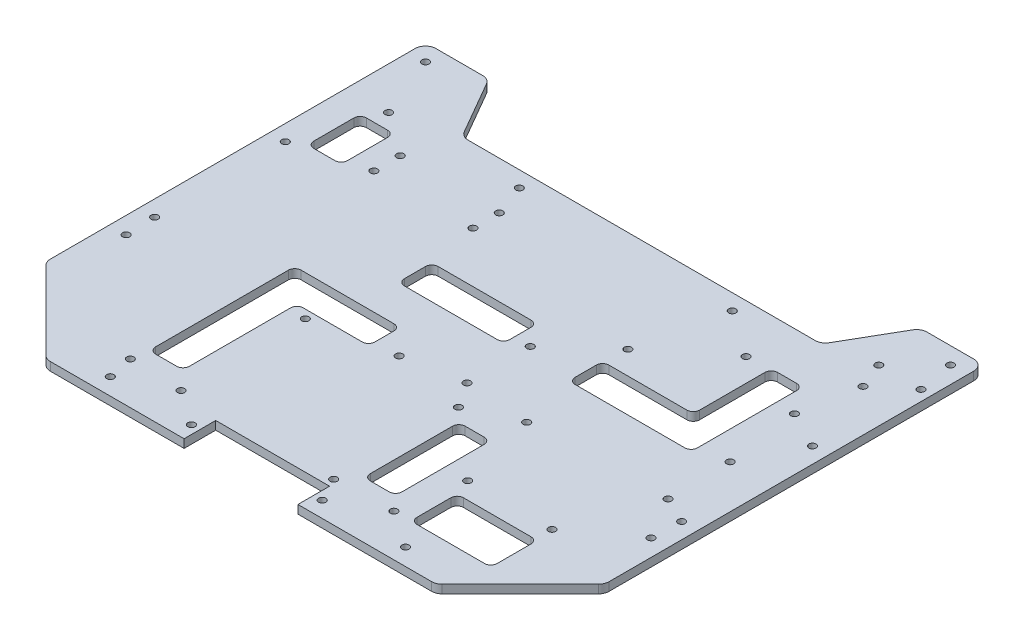
SolidWorks part; units mm, degrees
material "Acier non allié"
ref_plane "Front" through (0, 0, 0) normal (0, 0, 1) x (1, 0, 0)
ref_plane "Top" through (0, 0, 0) normal (0, 1, 0) x (1, 0, 0)
ref_plane "Right" through (0, 0, 0) normal (1, 0, 0) x (0, 0, -1)
sketch "Main scetch" plane through (0, 0, 0) normal (0, 1, 0) x (1, 0, 0)
  line L1 (0, 0) -> (132.5, 0) construction
  line L2 (0, 0) -> (0, 220) construction
  line L3 (0, 220) -> (132.5, 220) construction
  line L4 (132.5, 0) -> (132.5, 220) construction
  line L13 (-92.5, 0) -> (92.5, 0)
  line L14 (92.5, 0) -> (132.5, 40)
  line L15 (132.5, 40) -> (132.5, 220)
  line L16 (132.5, 220) -> (102.5, 220)
  line L17 (102.5, 220) -> (85.1795, 190)
  line L18 (85.1795, 190) -> (-85.1795, 190)
  line L19 (-102.5, 220) -> (-85.1795, 190)
  line L20 (-132.5, 220) -> (-102.5, 220)
  line L21 (-132.5, 40) -> (-132.5, 220)
  line L22 (-92.5, 0) -> (-132.5, 40)
  point P11 (0, 190)
  dimension "132.5" = 132.5
  dimension "D2" = 220
  dimension "D1" = 40
  dimension "D3" = 40
  dimension "D4" = 30
  dimension "D5" = 60
  dimension "D6" = 30
extrude "Main extrusion" add sketch "Main scetch" along normal blind 4
fillet "Congé1" radius 5 10 edges at (-132.5, 2, -40) (-92.5, 2, 0) (92.5, 2, 0) (132.5, 2, -40) (132.5, 2, -220) (102.5, 2, -220) (85.1795, 2, -190) (-85.1795, 2, -190) (-102.5, 2, -220) (-132.5, 2, -220)
sketch "Esquisse1" plane through (0, 4, 0) normal (0, 1, 0) x (1, 0, 0)
  line L0 (0, 0) -> (0, 218.5516) construction
  line L1 (132.5, 42.0711) -> (132.5, 215) construction
  line L2 (127.5, 220) -> (105.3868, 220) construction
  line L3 (-90.4289, 0) -> (90.4289, 0) construction
  circle A0 centre (70, 8) radius 1
  circle A1 centre (124.5, 70) radius 1
  circle A2 centre (124.5, 212) radius 1
  circle A3 centre (-124.5, 212) radius 1
  circle A4 centre (-124.5, 70) radius 1
  circle A5 centre (-70, 8) radius 1
  dimension "D1" = 2
  dimension "D2" = 2
  dimension "D3" = 2
  dimension "D4" = 8
  dimension "D5" = 8
  dimension "D6" = 8
  dimension "D7" = 8
  dimension "D8" = 70
  dimension "D9" = 70
extrude "Enlèv. mat.-Extru.1" cut sketch "Esquisse1" against normal through all
hole_wizard "Dégagement M31" positions "Esquisse2" profile "Esquisse3" hole size "M3" standard "ISO" end condition through all
sketch "Esquisse2" plane through (0, 4, 0) normal (0, 1, 0) x (1, 0, 0)
  point P0 (-124.5, 212)
  point P3 (-124.5, 70)
  point P6 (-70, 8)
  point P9 (70, 8)
  point P12 (124.5, 70)
  point P15 (124.5, 212)
sketch "Esquisse3" plane through (-124.5, 4, -212) normal (1, 0, 0) x (0, 0, 1)
  line L0 (0, 0) -> (0, 4)
  line L1 (0, 4) -> (1.7, 4)
  line L2 (1.7, 4) -> (1.7, 0)
  line L5 (1.7, 0) -> (0, 0)
  line L11 (0, -6.35) -> (0, 107.95) construction
  dimension "Diamètre du perçage jusqu'au prochain" = 3.4
  dimension "Profondeur du perçage jusqu'au prochain" = 4
sketch "Esquisse4" plane through (0, 4, 0) normal (0, 1, 0) x (1, 0, 0)
  line L0 (-132.5, 215) -> (-132.5, 42.0711) construction
  line L1 (-125, 146) -> (-125, 84) construction
  line L2 (82.2927, 190) -> (-82.2927, 190) construction
  line L3 (132.5, 42.0711) -> (132.5, 215) construction
  line L4 (-90.4289, 0) -> (90.4289, 0) construction
  line L5 (127.5, 220) -> (105.3868, 220) construction
  line L8 (-105.3868, 220) -> (-127.5, 220) construction
  line L9 (-31, 7.5) -> (31, 7.5) construction
  line L10 (125, 146) -> (125, 84) construction
  line L11 (-27, 0) -> (27, 0)
  line L12 (-27, 0) -> (-27, 15)
  line L13 (-27, 15) -> (27, 15)
  line L14 (27, 0) -> (27, 15)
  line L15 (50.5, 182.5) -> (112.5, 182.5) construction
  line L16 (-112.5, 182.5) -> (-50.5, 182.5) construction
  circle A1 centre (-68.5, 185) radius 1 construction
  circle A5 centre (72.5, 167) radius 1
  circle A6 centre (41.5, 142) radius 1
  circle A7 centre (107.5, 155) radius 1
  circle A8 centre (127.5, 195) radius 1
  circle A9 centre (112, 120) radius 1
  circle A10 centre (112.5, 90) radius 1
  circle A11 centre (17.2, 120) radius 1
  circle A12 centre (17.2, 90) radius 1
  circle A13 centre (47.5, 88) radius 1
  circle A14 centre (57.5, 50) radius 1
  circle A15 centre (97.5, 50) radius 1
  circle A16 centre (52.5, 20) radius 1
  circle A17 centre (-10, 85) radius 1
  circle A18 centre (-72.5, 20) radius 1
  circle A19 centre (107.5, 195) radius 1
  circle A23 centre (-47.5, 78) radius 1
  circle A24 centre (25.14, 78) radius 1
  circle A25 centre (-47.5, 19.07) radius 1
  circle A26 centre (25.1096, 18.82) radius 1
  circle A27 centre (-92, 167.5) radius 1
  circle A28 centre (-45, 167.5) radius 1
  circle A29 centre (-92, 155) radius 1
  circle A30 centre (-45, 155) radius 1
  circle A31 centre (-125, 146) radius 1
  circle A32 centre (-125, 84) radius 1
  circle A33 centre (-31, 7.5) radius 1
  circle A34 centre (31, 7.5) radius 1
  circle A35 centre (125, 146) radius 1
  circle A36 centre (125, 84) radius 1
  circle A37 centre (50.5, 182.5) radius 1
  circle A38 centre (112.5, 182.5) radius 1
  circle A39 centre (-112.5, 182.5) radius 1
  circle A40 centre (-50.5, 182.5) radius 1
  point P63 (-125, 115)
  point P69 (0, 7.5)
  point P74 (0, 15)
  point P79 (125, 115)
  dimension "D4" = 2
  dimension "D13" = 2
  dimension "D16" = 2
  dimension "D19" = 2
  dimension "D24" = 2
  dimension "D25" = 2
  dimension "D28" = 2
  dimension "D30" = 2
  dimension "D32" = 2
  dimension "D36" = 2
  dimension "D37" = 2
  dimension "D40" = 2
  dimension "D48" = 2
  dimension "D49" = 2
  dimension "D50" = 2
  dimension "D52" = 2
  dimension "D11" = 2
  dimension "D12" = 2
  dimension "D65" = 2
  dimension "D66" = 2
  dimension "D58" = 2
  dimension "D61" = 2
  dimension "D70" = 2
  dimension "D71" = 2
  dimension "D72" = 2
  dimension "D73" = 2
  dimension "D77" = 2
  dimension "D78" = 2
  dimension "D85" = 2
  dimension "D86" = 2
  dimension "D89" = 2
  dimension "D90" = 2
  dimension "D94" = 2
  dimension "D95" = 2
  dimension "D14" = 205
  dimension "D15" = 23
  dimension "D20" = 25
  dimension "D21" = 65
  dimension "D22" = 5
  dimension "D23" = 25
  dimension "D26" = 20.5
  dimension "D27" = 100
  dimension "D29" = 30
  dimension "D31" = 115.3
  dimension "D33" = 115.3
  dimension "D34" = 132
  dimension "D35" = 85
  dimension "D38" = 50
  dimension "D39" = 75
  dimension "D41" = 35
  dimension "D42" = 80
  dimension "D43" = 20
  dimension "D44" = 20
  dimension "D45" = 205
  dimension "D46" = 85
  dimension "D47" = 142.5
  dimension "D51" = 25
  dimension "D53" = 25
  dimension "D54" = 5
  dimension "D55" = 64
  dimension "D7" = 59.18
  dimension "D8" = 72.64
  dimension "D9" = 58.93
  dimension "D10" = 72.61
  dimension "D67" = 85
  dimension "D68" = 78
  dimension "D56" = 23.5
  dimension "D57" = 23.5
  dimension "D59" = 17.5
  dimension "D60" = 17.5
  dimension "D62" = 12.5
  dimension "D63" = 12.5
  dimension "D64" = 23.5
  dimension "D69" = 23.5
  dimension "D17" = 25
  dimension "D18" = 31
  dimension "D76" = 62
  dimension "D74" = 7.5
  dimension "D75" = 105
  dimension "D79" = 7.5
  dimension "D80" = 132.5
  dimension "D81" = 62
  dimension "D82" = 15
  dimension "D83" = 54
  dimension "D84" = 62
  dimension "D87" = 7.5
  dimension "D88" = 105
  dimension "D91" = 62
  dimension "D92" = 7.5
  dimension "D96" = 62
  dimension "D97" = 7.5
  dimension "D98" = 20
  dimension "D93" = 20
extrude "Enlèv. mat.-Extru.2" cut sketch "Esquisse4" against normal through all
hole_wizard "Dégagement M32" positions "Esquisse5" profile "Esquisse6" hole size "M3" standard "ISO" end condition through all
sketch "Esquisse5" plane through (0, 4, 0) normal (0, 1, 0) x (1, 0, 0)
  point P9 (17.2, 120)
  point P18 (41.5, 142)
  point P21 (72.5, 167)
  point P24 (107.5, 155)
  point P27 (127.5, 195)
  point P30 (112, 120)
  point P33 (112.5, 90)
  point P36 (47.5, 88)
  point P39 (17.2, 90)
  point P42 (57.5, 50)
  point P45 (97.5, 50)
  point P48 (-10, 85)
  point P51 (-72.5, 20)
  point P54 (52.5, 20)
  point P57 (107.5, 195)
  point P86 (-47.5, 78)
  point P89 (25.14, 78)
  point P92 (-47.5, 19.07)
  point P95 (25.1096, 18.82)
  point P102 (-92, 167.5)
  point P105 (-92, 155)
  point P108 (-45, 155)
  point P111 (-45, 167.5)
  point P114 (-125, 146)
  point P117 (-125, 84)
  point P121 (-31, 7.5)
  point P124 (31, 7.5)
  point P128 (125, 146)
  point P131 (125, 84)
  point P134 (-112.5, 182.5)
  point P137 (-50.5, 182.5)
  point P140 (50.5, 182.5)
  point P143 (112.5, 182.5)
sketch "Esquisse6" plane through (17.2, 4, -120) normal (1, 0, 0) x (0, 0, 1)
  line L0 (0, 0) -> (0, 4)
  line L1 (0, 4) -> (1.7, 4)
  line L2 (1.7, 4) -> (1.7, 0)
  line L5 (1.7, 0) -> (0, 0)
  line L11 (0, -6.35) -> (0, 107.95) construction
  dimension "Diamètre du perçage jusqu'au prochain" = 3.4
  dimension "Profondeur du perçage jusqu'au prochain" = 4
sketch "Esquisse7" plane through (0, 4, 0) normal (0, 1, 0) x (1, 0, 0)
  line L0 (-90.4289, 0) -> (-27, 0) construction
  line L1 (-40.5, 131) -> (9.5, 131)
  line L2 (-40.5, 131) -> (-40.5, 115)
  line L3 (-40.5, 115) -> (9.5, 115)
  line L4 (9.5, 131) -> (9.5, 115)
  line L5 (-132.5, 215) -> (-132.5, 42.0711) construction
  line L8 (40.5, 115) -> (98.5, 115)
  line L10 (132.5, 42.0711) -> (132.5, 215) construction
  line L11 (40.5, 115) -> (40.5, 131)
  line L12 (83.5, 168) -> (98.5, 168)
  line L13 (83.5, 168) -> (83.5, 131)
  line L15 (98.5, 168) -> (98.5, 115)
  line L16 (40.5, 131) -> (83.5, 131)
  line L17 (-105.3868, 220) -> (-127.5, 220) construction
  line L18 (60.5, 42) -> (98.5, 42)
  line L19 (60.5, 42) -> (60.5, 20)
  line L20 (60.5, 20) -> (98.5, 20)
  line L21 (98.5, 42) -> (98.5, 20)
  line L22 (-118.5, 175) -> (-102.5, 175)
  line L23 (-118.5, 175) -> (-118.5, 150)
  line L24 (-118.5, 150) -> (-102.5, 150)
  line L25 (-102.5, 175) -> (-102.5, 150)
  line L27 (-71.5, 28) -> (-55.5, 28)
  line L28 (-71.5, 28) -> (-71.5, 83)
  line L30 (-55.5, 28) -> (-55.5, 82)
  line L31 (31.5, 71.82) -> (46.5, 71.82)
  line L32 (31.5, 71.82) -> (31.5, 26.82)
  line L33 (31.5, 26.82) -> (46.5, 26.82)
  line L34 (46.5, 71.82) -> (46.5, 26.82)
  line L35 (-71.5, 97) -> (-21.5, 97)
  line L36 (-71.5, 97) -> (-71.5, 83)
  line L37 (-55.5, 82) -> (-21.5, 82)
  line L38 (-21.5, 97) -> (-21.5, 82)
  line L39 (-90.4289, 0) -> (-27, 0) construction
  circle A0 centre (-72.5, 20) radius 1.7 construction
  circle A1 centre (-47.5, 78) radius 1.7 construction
  circle A2 centre (25.1096, 18.82) radius 1.7 construction
  circle A3 centre (52.5, 20) radius 1.7 construction
  point P44 (-72.7212, 83)
  point P48 (-70.5, 86.1006)
  point P49 (-73.5, 83.543)
  point P50 (-70.5, 84.2405)
  point P51 (-73.4049, 83)
  dimension "D19" = 8
  dimension "D20" = 8
  dimension "D24" = 15
  dimension "D1" = 50
  dimension "D2" = 16
  dimension "D3" = 131
  dimension "D4" = 92
  dimension "D5" = 16
  dimension "D6" = 53
  dimension "D7" = 43
  dimension "D8" = 115
  dimension "D9" = 72
  dimension "D10" = 38
  dimension "D11" = 34
  dimension "D12" = 15
  dimension "D13" = 22
  dimension "D14" = 20
  dimension "D15" = 30
  dimension "D16" = 70
  dimension "D17" = 16
  dimension "D18" = 25
  dimension "D21" = 16
  dimension "D22" = 55
  dimension "D23" = 8
  dimension "6" = 6
  dimension "D25" = 45
  dimension "D26" = 50
  dimension "D27" = 54
  dimension "D28" = 15
extrude "Enlèv. mat.-Extru.3" cut sketch "Esquisse7" against normal up to surface (4 mm away) up to face at (17.2, 0, -118.3)
fillet "Congé2" radius 3 28 edges at (60.5, 2, -42) (60.5, 2, -20) (98.5, 2, -20) (98.5, 2, -42) (98.5, 2, -168) (98.5, 2, -115) (83.5, 2, -168) (40.5, 2, -131) (83.5, 2, -131) (40.5, 2, -115) (-40.5, 2, -115) (9.5, 2, -115) (9.5, 2, -131) (-40.5, 2, -131) (-118.5, 2, -150) (-102.5, 2, -150) (-102.5, 2, -175) (-118.5, 2, -175) (-55.5, 2, -28) (-71.5, 2, -28) (46.5, 2, -26.82) (31.5, 2, -26.82) (46.5, 2, -71.82) (31.5, 2, -71.82) (-21.5, 2, -82) (-21.5, 2, -97) (-55.5, 2, -82) (-71.5, 2, -97)
equation "\"WIDTH\"= 300mm'Total width of the robot"
equation "\"LENGTH\"= 220mm'Total length of the robot"
equation "\"D2@Main scetch\" = \"LENGTH\""
equation "\"CUT_DEPTH\"= 45mm'Depth of the cut on the edges of the plate"
equation "\"Plate_th\"= 3mm'Thickness of the plate"
equation "\"D1\"= \"Plate_th\""
equation "\"D47@Esquisse4\"=(80+205)/2"
